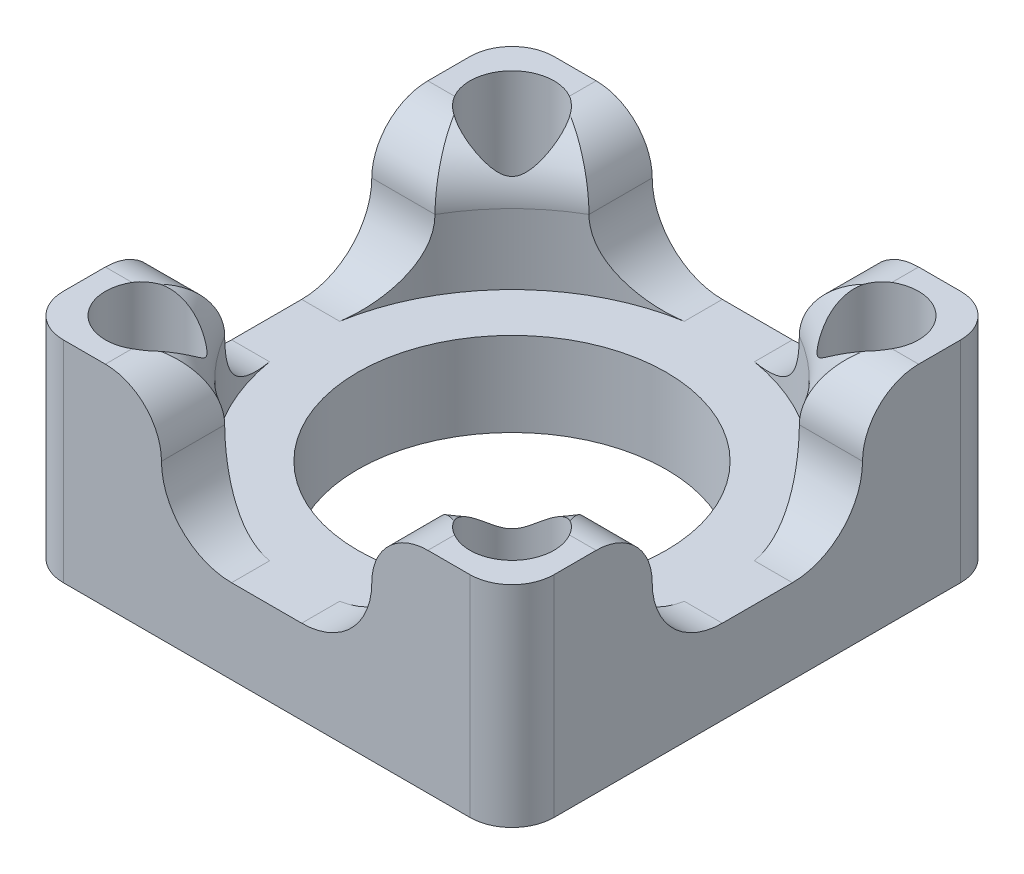
SolidWorks part; units mm, degrees
ref_plane "Front Plane" through (0, 0, 0) normal (0, 0, 1) x (1, 0, 0)
ref_plane "Top Plane" through (0, 0, 0) normal (0, 1, 0) x (1, 0, 0)
ref_plane "Right Plane" through (0, 0, 0) normal (1, 0, 0) x (0, 0, -1)
sketch "Sketch1" plane through (0, 0, 0) normal (0, 1, 0) x (1, 0, 0)
  line L1 (-20.9211, 7.6974) -> (14.0789, 7.6974)
  line L2 (-20.9211, 7.6974) -> (-20.9211, -27.3026)
  line L3 (-20.9211, -27.3026) -> (14.0789, -27.3026)
  line L4 (14.0789, 7.6974) -> (14.0789, -27.3026)
  dimension "D1" = 35
  dimension "D2" = 35
extrude "Boss-Extrude1" add sketch "Sketch1" along normal blind 6
fillet "Fillet1" radius 3 4 edges at (-20.9211, 3, -7.6974) (14.0789, 3, -7.6974) (14.0789, 3, 27.3026) (-20.9211, 3, 27.3026)
sketch "Sketch2" plane through (0, 6, 0) normal (0, 1, 0) x (1, 0, 0)
  line L0 (-20.9211, 4.6974) -> (-20.9211, -24.3026) construction
  line L1 (11.0789, 7.6974) -> (-17.9211, 7.6974) construction
  circle A0 centre (-16.4211, 3.1974) radius 2.25
  circle A1 centre (9.5789, 3.1974) radius 2.25
  circle A2 centre (9.5789, -22.8026) radius 2.25
  circle A3 centre (-16.4211, -22.8026) radius 2.25
  dimension "D1" = 4.5
  dimension "D2" = 4.5
  dimension "D3" = 4.5
  dimension "D6" = 26
  dimension "D7" = 26
  dimension "D4" = 2
  dimension "D5" = 2
extrude "Cut-Extrude1" cut sketch "Sketch2" against normal up to next and the other way through all
sketch "Sketch3" plane through (0, 6, 0) normal (0, 1, 0) x (1, 0, 0)
  line L0 (14.0789, -24.3026) -> (14.0789, 4.6974) construction
  line L1 (-17.9211, -27.3026) -> (11.0789, -27.3026) construction
  circle A0 centre (-3.4211, -9.8026) radius 11
  point P2 (0, 0)
  point P5 (0, 0)
  point P7 (-0.9616, -18.6078)
  dimension "D1" = 22
  dimension "D2" = 17.5
  dimension "D3" = 17.5
extrude "Cut-Extrude2" cut sketch "Sketch3" against normal up to next
sketch "Sketch4" plane through (0, 6, 0) normal (0, 1, 0) x (1, 0, 0)
  line L0 (11.0789, 7.6974) -> (-17.9211, 7.6974) construction
  line L1 (-20.9211, 4.6974) -> (-20.9211, -24.3026) construction
  line L2 (-17.9211, -27.3026) -> (11.0789, -27.3026) construction
  line L3 (14.0789, -24.3026) -> (14.0789, 4.6974) construction
  line L4 (11.0789, 7.6974) -> (-17.9211, 7.6974)
  line L5 (-20.9211, 4.6974) -> (-20.9211, -24.3026)
  line L6 (-17.9211, -27.3026) -> (11.0789, -27.3026)
  line L7 (14.0789, -24.3026) -> (14.0789, 4.6974)
  arc A0 (-17.9211, 7.6974) -> (-20.9211, 4.6974) centre (-17.9211, 4.6974) ccw construction
  arc A1 (-20.9211, -24.3026) -> (-17.9211, -27.3026) centre (-17.9211, -24.3026) ccw construction
  arc A2 (11.0789, -27.3026) -> (14.0789, -24.3026) centre (11.0789, -24.3026) ccw construction
  arc A3 (14.0789, 4.6974) -> (11.0789, 7.6974) centre (11.0789, 4.6974) ccw construction
  arc A4 (-17.9211, 7.6974) -> (-20.9211, 4.6974) centre (-17.9211, 4.6974) ccw
  arc A5 (-20.9211, -24.3026) -> (-17.9211, -27.3026) centre (-17.9211, -24.3026) ccw
  arc A6 (11.0789, -27.3026) -> (14.0789, -24.3026) centre (11.0789, -24.3026) ccw
  arc A7 (14.0789, 4.6974) -> (11.0789, 7.6974) centre (11.0789, 4.6974) ccw
  circle A8 centre (-3.4211, -9.8026) radius 15
  circle A9 centre (9.5789, 3.1974) radius 2.25 construction
  circle A10 centre (9.5789, -22.8026) radius 2.25 construction
  circle A11 centre (-16.4211, -22.8026) radius 2.25 construction
  circle A12 centre (-16.4211, 3.1974) radius 2.25 construction
  circle A13 centre (9.5789, 3.1974) radius 2.25
  circle A14 centre (9.5789, -22.8026) radius 2.25
  circle A15 centre (-16.4211, -22.8026) radius 2.25
  circle A16 centre (-16.4211, 3.1974) radius 2.25
  dimension "D1" = 30
extrude "Boss-Extrude2" add sketch "Sketch4" along normal blind 9
sketch "Sketch5" plane through (0, 0, 27.3026) normal (0, 0, 1) x (1, 0, 0)
  line L0 (-10.9211, 15) -> (4.0789, 15)
  line L1 (-17.9211, 15) -> (11.0789, 15) construction
  line L2 (-20.9211, 0) -> (-20.9211, 15) construction
  line L3 (14.0789, 15) -> (14.0789, 0) construction
  line L4 (-10.9211, 15) -> (-10.9211, 6)
  line L5 (-10.9211, 6) -> (4.0789, 6)
  line L6 (4.0789, 6) -> (4.0789, 15)
  line L7 (-17.9211, 0) -> (11.0789, 0) construction
  dimension "D1" = 10
  dimension "D2" = 10
  dimension "D3" = 6
extrude "Cut-Extrude3" cut sketch "Sketch5" against normal through all
sketch "Sketch6" plane through (-20.9211, 0, 0) normal (-1, 0, 0) x (0, 0, 1)
  line L0 (-4.6974, 15) -> (24.3026, 15) construction
  line L1 (2.3026, 15) -> (17.3026, 15)
  line L2 (2.3026, 15) -> (2.3026, 6)
  line L3 (2.3026, 6) -> (17.3026, 6)
  line L4 (17.3026, 15) -> (17.3026, 6)
  line L5 (-7.6974, 0) -> (-7.6974, 15) construction
  dimension "D1" = 15
  dimension "D2" = 10
  dimension "D3" = 9
extrude "Cut-Extrude4" cut sketch "Sketch6" against normal through all
fillet "Fillet2" radius 4 12 edges at (-18.6662, 15, 17.3026) (-10.9211, 15, 25.0478) (4.0789, 15, 25.0478) (11.8241, 15, 17.3026) (11.8241, 15, 2.3026) (4.0789, 15, -5.4426) (-10.9211, 15, -5.4426) (-18.6662, 15, 2.3026) (-14.0277, 15, 20.4092) (-14.0277, 15, -0.804) (7.1855, 15, 20.4092) (7.1855, 15, -0.804)
fillet "Fillet3" radius 5 8 edges at (-10.9211, 6, 25.0478) (-18.6662, 6, 17.3026) (-10.9211, 6, -5.4426) (11.8241, 6, 17.3026) (4.0789, 6, 25.0478) (11.8241, 6, 2.3026) (4.0789, 6, -5.4426) (-18.6662, 6, 2.3026)
sketch "Sketch7" plane through (0, 15, 0) normal (0, 1, 0) x (1, 0, 0)
  circle A0 centre (9.5789, -22.8026) radius 3
  circle A1 centre (-16.4211, -22.8026) radius 3
  circle A3 centre (9.5789, 3.1974) radius 3
  circle A4 centre (-16.4211, 3.1974) radius 3
  dimension "D1" = 6
extrude "Cut-Extrude5" cut sketch "Sketch7" against normal blind 9
